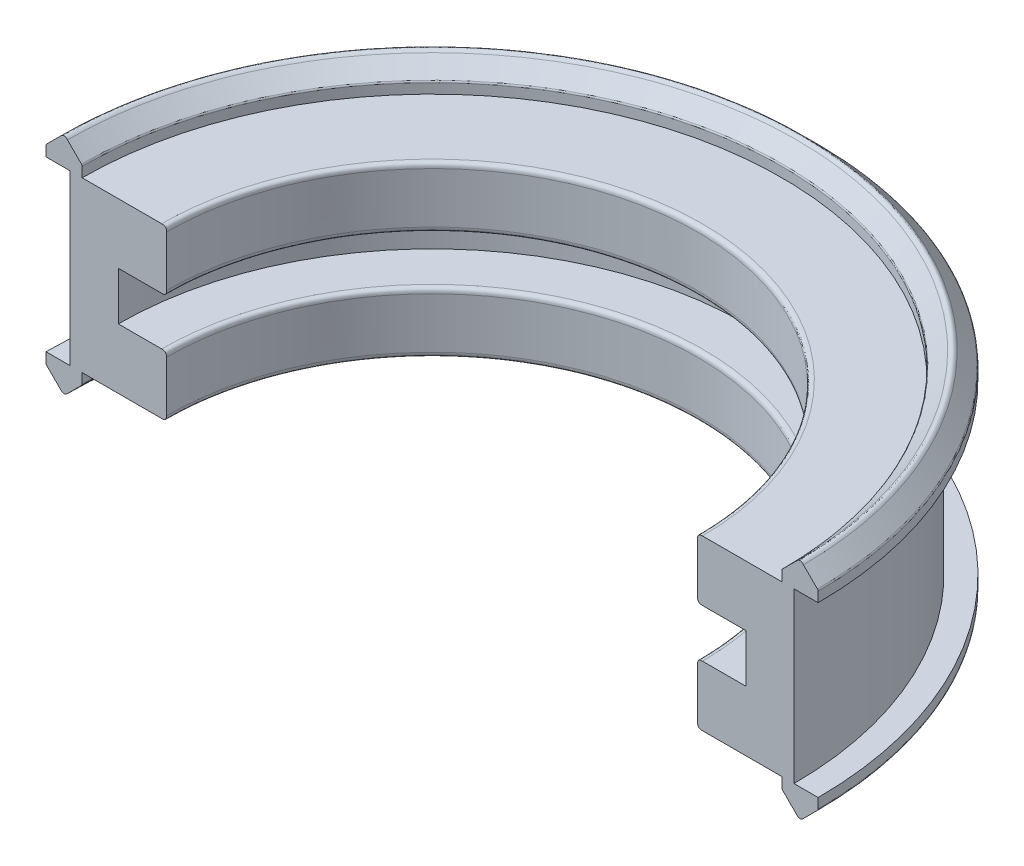
SolidWorks part; units mm, degrees
ref_plane "Front Plane" through (0, 0, 0) normal (0, 0, 1) x (1, 0, 0)
ref_plane "Top Plane" through (0, 0, 0) normal (0, 1, 0) x (1, 0, 0)
ref_plane "Right Plane" through (0, 0, 0) normal (1, 0, 0) x (0, 0, -1)
sketch "Sketch1" plane through (0, 0, 0) normal (0, 0, 1) x (1, 0, 0)
  line L0 (-27.5676, 0) -> (63.7838, 0) construction
  line L1 (-20, 17.5) -> (-20, -17.5)
  line L2 (-20, -17.5) -> (-25, -17.5)
  line L3 (-25, -17.5) -> (-25, -19.75)
  line L4 (-25, -19.75) -> (-21.25, -23.5)
  line L5 (-21.25, -23.5) -> (-17.5, -19.75)
  line L6 (-17.5, -19.75) -> (-17.5, -17.5)
  line L7 (-17.5, -17.5) -> (0, -17.5)
  line L8 (0, -17.5) -> (0, -5)
  line L9 (0, -5) -> (-10, -5)
  line L10 (-10, -5) -> (-10, 5)
  line L11 (-10, 5) -> (0, 5)
  line L12 (0, 5) -> (0, 17.5)
  line L13 (0, 17.5) -> (-17.5, 17.5)
  line L14 (-17.5, 17.5) -> (-17.5, 19.75)
  line L15 (-17.5, 19.75) -> (-21.25, 23.5)
  line L16 (-21.25, 23.5) -> (-25, 19.75)
  line L17 (-25, 19.75) -> (-25, 17.5)
  line L18 (-25, 17.5) -> (-20, 17.5)
  point P32 (-22.5, 17.5)
  dimension "D1" = 25
  dimension "D2" = 47
  dimension "D3" = 35
  dimension "D4" = 35
  dimension "D5" = 3.75
  dimension "D6" = 3.75
  dimension "D7" = 10
  dimension "D8" = 10
  dimension "D9" = 20
sketch "Sketch27" plane through (0, 0, 0) normal (0, 1, 0) x (1, 0, 0)
  line L0 (-200027.5676, 0) -> (200063.7838, 0) construction
  arc A0 (-19.9048, 0) -> (130.0952, 0) centre (55.0952, 0) cw
  point P3 (0, 0)
  point P6 (58.6515, 0)
  point P7 (60.2629, 0)
  dimension "D1" = 150
sweep "Sweep6" add profiles "Sketch1" path "Sketch27"
fillet "Fillet9" radius 1 1 edges at (55.0952, -23.5, -76.3452) curvature continuous yes
fillet "Fillet10" radius 1 1 edges at (55.0952, 23.5, -76.3452) curvature continuous yes
fillet "Fillet11" radius 0.5 1 edges at (55.0952, 19.75, -80.0952) curvature continuous yes
fillet "Fillet12" radius 0.5 1 edges at (55.0952, 19.75, -72.5952) curvature continuous yes
fillet "Fillet13" radius 0.5 1 edges at (55.0952, -19.75, -80.0952) curvature continuous yes
fillet "Fillet14" radius 0.5 1 edges at (55.0952, -19.75, -72.5952) curvature continuous yes
fillet "Fillet15" radius 1 4 edges at (55.0952, -5, -55.0952) (55.0952, 5, -55.0952) (55.0952, -17.5, -55.0952) (55.0952, 17.5, -55.0952) curvature continuous yes
